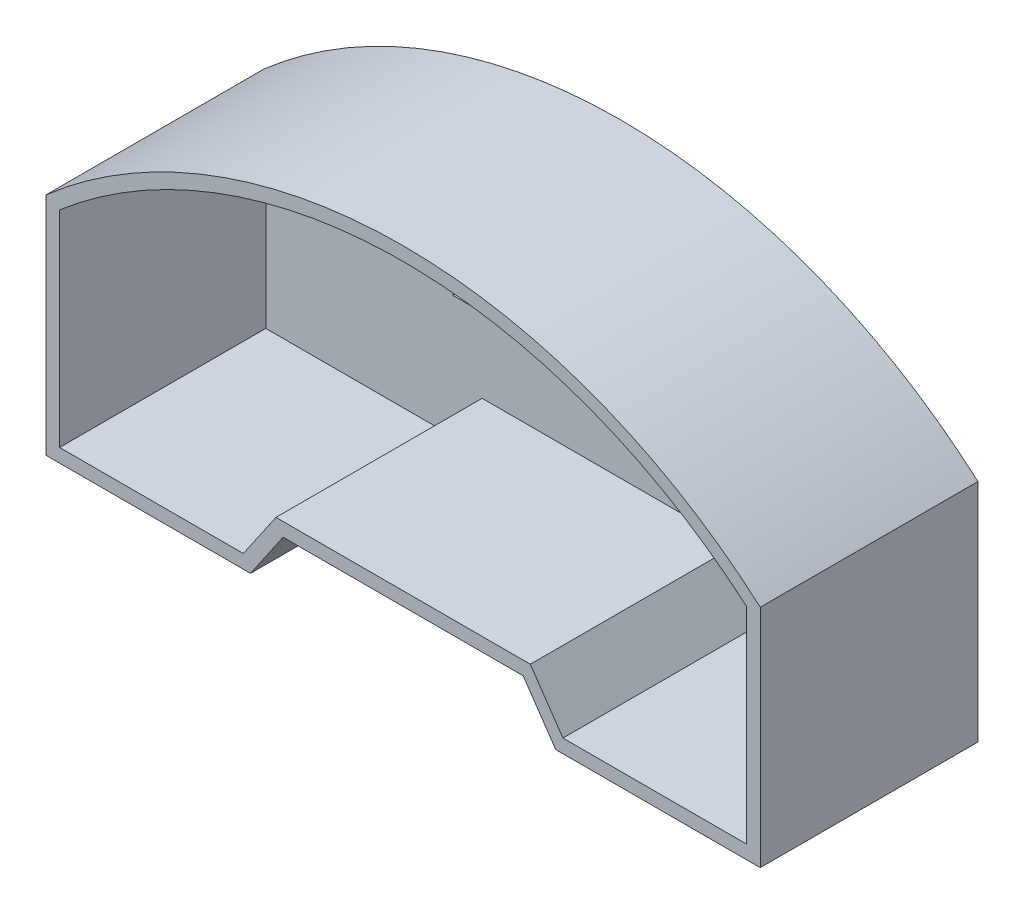
SolidWorks part; units mm, degrees
ref_plane "Front Plane" through (0, 0, 0) normal (0, 0, 1) x (1, 0, 0)
ref_plane "Top Plane" through (0, 0, 0) normal (0, 1, 0) x (1, 0, 0)
ref_plane "Right Plane" through (0, 0, 0) normal (1, 0, 0) x (0, 0, -1)
sketch "Model" plane through (0, 0, 0) normal (0, 0, 1) x (1, 0, 0)
  line L0 (323.8195, 86.1332) -> (342.4467, 86.1332)
  line L1 (133.9554, 86.1332) -> (119.1392, 86.1332)
  line L2 (138.7179, 94.5948) -> (138.7179, 90.8957)
  line L3 (177.2382, 143.8987) -> (176.3071, 143.3211)
  line L4 (174.6348, 142.6586) -> (173.6571, 142.4612)
  line L5 (287.9242, 142.4621) -> (286.9498, 142.6588)
  line L6 (285.2787, 143.3205) -> (284.3173, 143.9163)
  line L7 (162.847, 94.6988) -> (162.847, 74.93)
  line L8 (280.8118, 88.4213) -> (261.3502, 83.8178)
  line L9 (279.6237, 74.93) -> (283.771, 75.911)
  line L10 (287.5452, 82.0239) -> (286.9248, 84.647)
  line L11 (323.8195, 94.5947) -> (323.8195, 86.1332)
  line L12 (303.8174, 74.93) -> (303.8171, 81.4992)
  line L13 (303.4001, 83.5146) -> (300.6799, 89.8076)
  line L14 (194.8621, 74.93) -> (201.9402, 86.7276)
  line L15 (223.7209, 99.06) -> (238.0024, 99.06)
  line L16 (260.5319, 85.3896) -> (261.3502, 83.8178)
  arc A0 (284.3173, 143.9163) -> (177.2382, 143.8987) centre (230.792, 57.5589) ccw
  arc A1 (346.8935, 92.6009) -> (287.9242, 142.4621) centre (272.0679, 63.9082) ccw
  arc A2 (173.6571, 142.4612) -> (114.6924, 92.6009) centre (189.5179, 63.9082) ccw
  arc A3 (323.8195, 94.5947) -> (300.6799, 89.8076) centre (311.7545, 94.5947) ccw
  arc A4 (162.847, 94.6988) -> (138.7179, 94.5948) centre (150.7829, 94.5553) ccw
  arc A5 (114.6924, 92.6009) -> (119.1392, 86.1332) centre (119.1392, 90.8957) ccw
  arc A6 (133.9554, 86.1332) -> (138.7179, 90.8957) centre (133.9554, 90.8957) ccw
  arc A7 (342.4467, 86.1332) -> (346.8935, 92.6009) centre (342.4467, 90.8957) ccw
  arc A8 (174.6348, 142.6586) -> (176.3071, 143.3211) centre (173.6294, 147.6381) ccw
  arc A9 (285.2787, 143.3205) -> (286.9498, 142.6588) centre (287.955, 147.6383) ccw
  arc A10 (286.9248, 84.647) -> (280.8118, 88.4213) centre (281.9812, 83.4777) ccw
  arc A11 (283.771, 75.911) -> (287.5452, 82.0239) centre (282.6016, 80.8546) ccw
  arc A12 (303.8171, 81.4992) -> (303.4001, 83.5146) centre (298.7371, 81.4989) ccw
  arc A13 (223.7209, 99.06) -> (201.9402, 86.7276) centre (223.7209, 73.66) ccw
  arc A14 (260.5319, 85.3896) -> (238.0024, 99.06) centre (238.0024, 73.66) ccw
sketch "Sketch2" plane through (0, 0, 0) normal (0, 0, 1) x (1, 0, 0)
  line L0 (166.657, 132.3824) -> (166.657, 93.98)
  line L1 (348.5671, 99.06) -> (147.7497, 99.06) construction
  line L2 (166.657, 93.98) -> (200.947, 93.98)
  line L3 (200.947, 93.98) -> (207.0377, 102.87)
  line L4 (207.0377, 102.87) -> (254.5128, 102.87)
  line L5 (230.7752, 159.1589) -> (230.7752, 57.6178) construction
  line L6 (230.7752, 99.06) -> (230.7752, 156.1109) construction
  line L7 (260.6035, 93.98) -> (254.5128, 102.87)
  line L8 (294.8935, 93.98) -> (260.6035, 93.98)
  line L9 (294.8935, 132.3824) -> (294.8935, 93.98)
  line L11 (259.9852, 116.784) -> (244.7452, 116.784)
  line L12 (259.9852, 116.784) -> (259.9852, 137.104)
  line L13 (259.9852, 137.104) -> (244.7452, 137.104)
  line L14 (244.7452, 116.784) -> (244.7452, 137.104)
  line L15 (201.5652, 137.104) -> (216.8052, 137.104)
  line L16 (201.5652, 116.784) -> (201.5652, 137.104)
  line L17 (201.5652, 116.784) -> (216.8052, 116.784)
  line L18 (216.8052, 116.784) -> (216.8052, 137.104)
  line L19 (238.3952, 116.784) -> (223.1552, 116.784)
  line L20 (238.3952, 116.784) -> (238.3952, 137.104)
  line L21 (238.3952, 137.104) -> (223.1552, 137.104)
  line L22 (223.1552, 116.784) -> (223.1552, 137.104)
  arc A0 (284.3173, 143.9163) -> (177.2382, 143.8987) centre (230.792, 57.5589) ccw construction
  arc A2 (294.8935, 132.3824) -> (166.657, 132.3824) centre (230.7752, 57.6178) ccw
  point P12 (230.7752, 159.1589)
  point P19 (230.7752, 102.87)
  point P34 (230.7752, 137.104)
  dimension "D6" = 20.32
  dimension "D1" = 3.81
  dimension "D2" = 5.08
  dimension "D3" = 3.81
  dimension "D4" = 34.29
  dimension "D5" = 10.7763
  dimension "D7" = 3.048
  dimension "D8" = 15.24
  dimension "D9" = 20.32
  dimension "D10" = 15.24
  dimension "D11" = 13.914
  dimension "D12" = 6.35
extrude "Boss-Extrude4" add sketch "Sketch2" along normal blind 2.159
extrude "Extrude-Thin2" add sketch "Sketch2<7>" along normal blind 40.64 thin contours L4 L7 L8 L9 A2 L0 L2 L3 thin type one direction wall 2.54
sketch "Sketch2<7>" plane through (0, 0, 0) normal (0, 0, 1) x (1, 0, 0) same geometry as "Sketch2"
